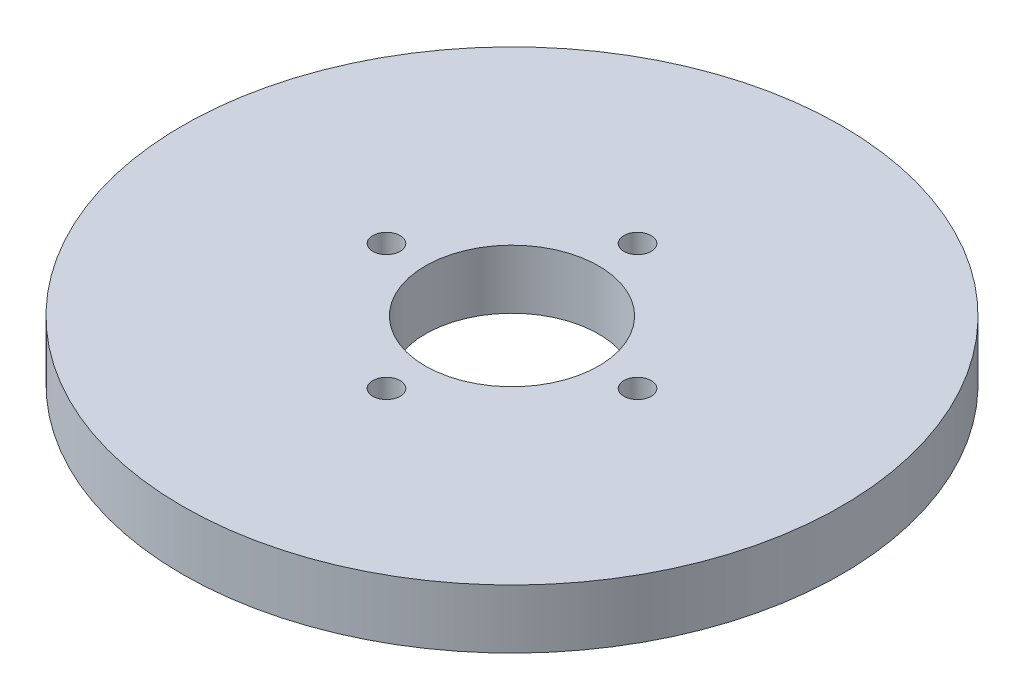
SolidWorks part; units mm, degrees
ref_plane "Front Plane" through (0, 0, 0) normal (0, 0, 1) x (1, 0, 0)
ref_plane "Top Plane" through (0, 0, 0) normal (0, 1, 0) x (1, 0, 0)
ref_plane "Right Plane" through (0, 0, 0) normal (1, 0, 0) x (0, 0, -1)
sketch "Sketch1" plane through (0, 0, 0) normal (0, 1, 0) x (1, 0, 0)
  circle A0 centre (0, 0) radius 95
  dimension "FLANGE_OD" = 190
extrude "Boss-Extrude1" add sketch "Sketch1" along normal blind 17
sketch "Sketch2" plane through (0, 0, 0) normal (0, 1, 0) x (1, 0, 0)
  circle A0 centre (0, 0) radius 25
  dimension "BORE_D" = 50
extrude "Cut-Extrude1" cut sketch "Sketch2" along normal through all
sketch "Sketch3" plane through (0, 17, 0) normal (0, 1, 0) x (1, 0, 0)
  circle A0 centre (0, 0) radius 36.186 construction
  circle A1 centre (-36.186, 0) radius 3.9444
  dimension "BOLT_D" = 7.8889
  dimension "BOLT_PCD" = 72.3719
extrude "Cut-Extrude2" cut sketch "Sketch3" against normal blind 15.7763
pattern_circular "CirPattern1" count 4 over 360 about axis through (0, 0, 0) along (0, 1, 0) of "Cut-Extrude2"
